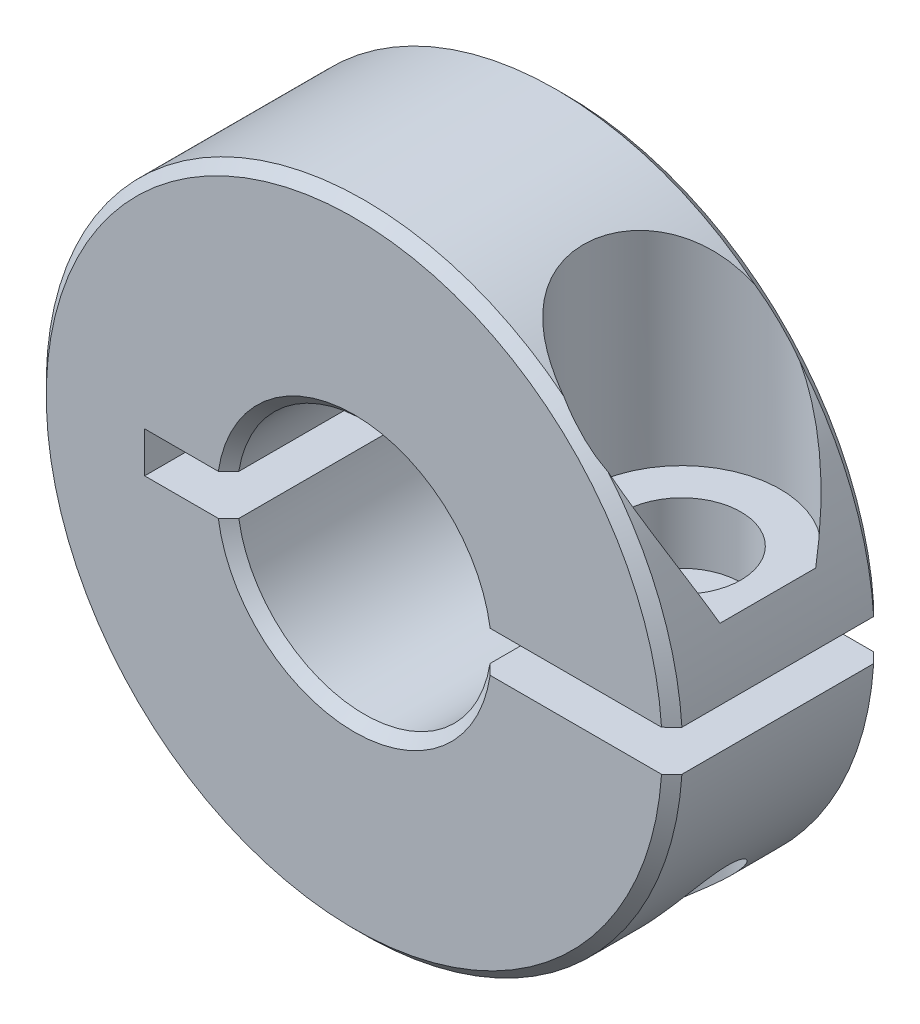
SolidWorks part; units mm, degrees
material "6061-T6 (SS)"
ref_plane "Front" through (0, 0, 0) normal (0, 0, 1) x (1, 0, 0)
ref_plane "Top" through (0, 0, 0) normal (0, 1, 0) x (1, 0, 0)
ref_plane "Right" through (0, 0, 0) normal (1, 0, 0) x (0, 0, -1)
ref_axis "side-side" through (80.9, 0, 0) along (-1, 0, 0)
ref_axis "up-down" through (0, 50, 0) along (0, -1, 0)
ref_axis "front-back" through (0, 0, -80.9) along (0, 0, 1)
sketch "Sketch1" plane through (0, 0, 0) normal (0, 0, 1) x (1, 0, 0)
  line L0 (-7.8422, 0) -> (0, 0) construction
  line L1 (-7.8422, 0.762) -> (-4.7011, 0.762)
  line L2 (-7.8422, 0.762) -> (-7.8422, -0.762)
  line L3 (-7.8422, -0.762) -> (-4.7011, -0.762)
  line L4 (4.7011, -0.762) -> (11.8818, -0.762)
  line L5 (4.7011, 0.762) -> (11.8818, 0.762)
  arc A0 (11.8818, 0.762) -> (11.8818, -0.762) centre (0, 0) ccw
  arc A1 (4.7011, 0.762) -> (-4.7011, 0.762) centre (0, 0) ccw
  arc A2 (-4.7011, -0.762) -> (4.7011, -0.762) centre (0, 0) ccw
  dimension "D1" = 9.525
  dimension "D2" = 23.8125
  dimension "D3" = 1.524
  dimension "D4" = 4.064
extrude "Boss-Extrude1" add sketch "Sketch1" along normal mid plane 7.9375
hole_wizard "#8-32 Tapped Hole1" positions "Sketch2" profile "Sketch4" tap size "#8-32" standard "ANSI Inch" end condition through all
sketch "Sketch2" plane through (0, -0.762, 0) normal (0, 1, 0) x (1, 0, 0)
  line L0 (11.8818, -3.9688) -> (4.7011, 3.9688) construction
  point P0 (8.2915, 0)
  point P6 (0, 0)
sketch "Sketch4" plane through (8.2915, -0.762, 0) normal (1, 0, 0) x (0, 0, 1)
  line L0 (0, 0) -> (0, 11.1442)
  line L1 (0, 11.1442) -> (1.7272, 11.1442)
  line L2 (1.7272, 11.1442) -> (1.7272, 0)
  line L5 (1.7272, 0) -> (0, 0)
  line L11 (0, -6.35) -> (0, 107.95) construction
  dimension "Thread Major Dia." = 3.4544
  dimension "Thru Tap Drill Depth" = 11.1442
sketch "Sketch5" plane through (0, 0.762, 0) normal (0, -1, 0) x (1, 0, 0)
  circle A0 centre (8.2915, 0) radius 1.27
  dimension "D1" = 2.54
chamfer "Chamfer1" distance 0.381 angle 45 6 edges at (-11.9062, 0, -3.9688) (0, -4.7625, -3.9688) (0, 4.7625, -3.9688) (-11.9062, 0, 3.9688) (0, -4.7625, 3.9688) (0, 4.7625, 3.9688)
sketch "Sketch10" plane through (0, 0, 0) normal (0, 0, 1) x (1, 0, 0)
  line L0 (8.2915, -0.762) -> (8.2915, -11.9948) construction
  line L1 (5.0867, 0.762) -> (11.5, 0.762) construction
  line L2 (8.2915, 0.762) -> (10.5013, 0.762)
  line L3 (8.2915, 0.762) -> (8.2915, 11.9062)
  line L4 (8.2915, 11.9062) -> (11.9745, 11.9062)
  line L5 (10.5013, 0.762) -> (10.5013, 3.048)
  line L6 (4.7011, 0.762) -> (11.8818, 0.762) construction
  line L7 (10.5013, 3.048) -> (11.9745, 3.048)
  line L10 (11.9745, 3.048) -> (11.9745, 11.9062)
  arc A0 (11.8818, -0.762) -> (-11.8818, 0.762) centre (0, 0) ccw construction
  point P14 (0, 0)
  dimension "D1" = 7.366
  dimension "D2" = 4.4196
  dimension "D3" = 2.286
revolve "Cut-Revolve1" cut sketch "Sketch10" angle 360 about L0
